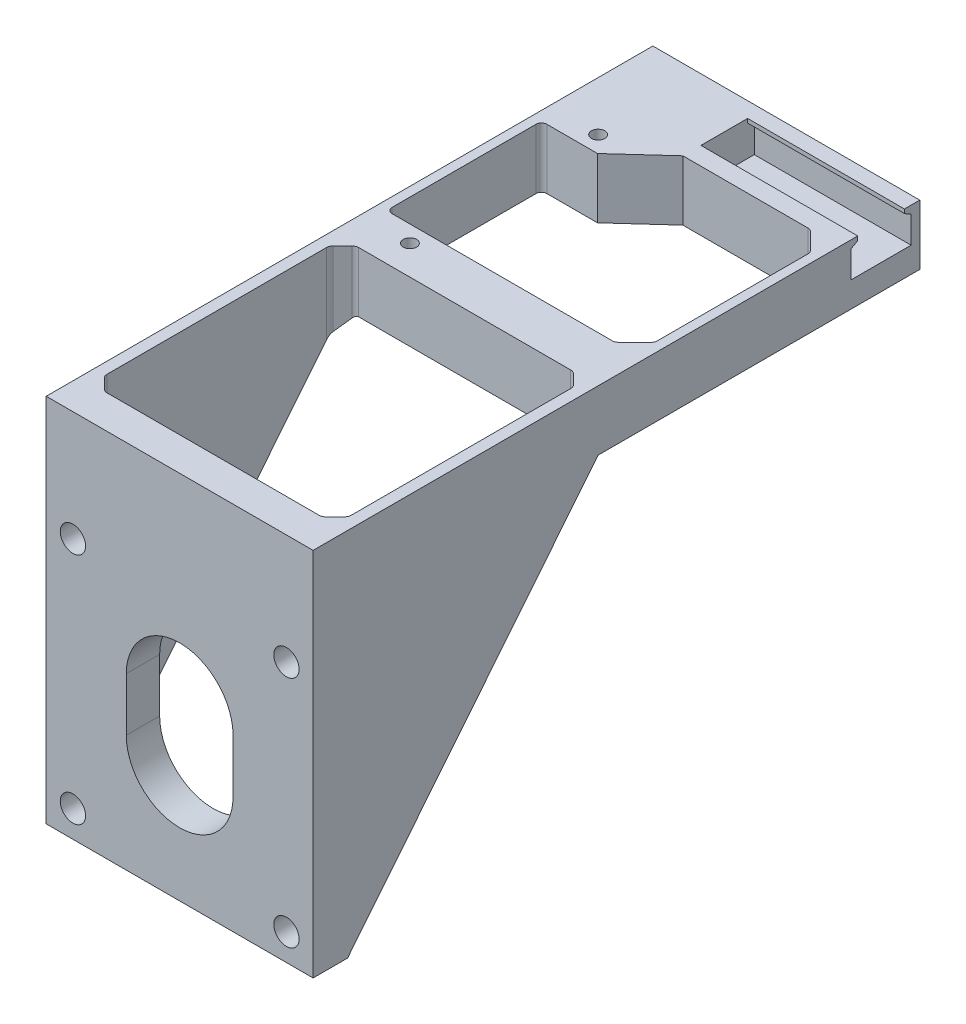
SolidWorks part; units mm, degrees
ref_plane "Front Plane" through (0, 0, 0) normal (0, 0, 1) x (1, 0, 0)
ref_plane "Top Plane" through (0, 0, 0) normal (0, 1, 0) x (1, 0, 0)
ref_plane "Right Plane" through (0, 0, 0) normal (1, 0, 0) x (0, 0, -1)
sketch "Sketch1" plane through (0, 0, 0) normal (0, 1, 0) x (1, 0, 0)
  line L0 (0, 0) -> (0, 59.6401) construction
  line L1 (-20, -19.2885) -> (-21.4, -19.2885)
  line L2 (20, 17.7115) -> (21.4, 17.7115)
  line L3 (20, 17.7115) -> (20, 69.9115)
  line L4 (20, 69.9115) -> (21.4, 69.9115)
  line L5 (21.4, 17.7115) -> (21.4, 69.9115)
  line L6 (20, 17.7115) -> (21.4, 17.7115)
  line L7 (20, 17.7115) -> (20, -19.2885)
  line L8 (20, -19.2885) -> (21.4, -19.2885)
  line L9 (21.4, 17.7115) -> (21.4, -19.2885)
  line L10 (-21.4, 17.7115) -> (-21.4, -19.2885)
  line L11 (-20, 17.7115) -> (-21.4, 17.7115)
  line L12 (-20, 17.7115) -> (-20, -19.2885)
  line L13 (-20, 69.9115) -> (-21.4, 69.9115)
  line L14 (-21.4, 17.7115) -> (-21.4, 69.9115)
  line L15 (-20, 17.7115) -> (-21.4, 17.7115)
  line L16 (-20, 17.7115) -> (-20, 69.9115)
  dimension "18" = 20
  dimension "D2" = 1.4
  dimension "D3" = 37
  dimension "D4" = 52.2
extrude "Boss-Extrude1" add sketch "Sketch1" against normal blind 9 from offset 1 contours L12 L11 L10 L1 | L11 L16 L13 L14 | L3 L2 L5 L4 offset against normal yes
sketch "Sketch4" plane through (0, -10, 0) normal (0, -1, 0) x (1, 0, 0)
  line L0 (-21.4, -69.9115) -> (-21.4, 19.2885) construction
  line L1 (18.6, -69.9115) -> (-21.4, -69.9115)
  line L2 (18.6, -69.9115) -> (18.6, -57.9115)
  line L3 (18.6, -57.9115) -> (-21.4, -57.9115)
  line L4 (-21.4, -69.9115) -> (-21.4, -57.9115)
  line L13 (-20, -69.9115) -> (-21.4, -69.9115) construction
  dimension "D1" = 12
  dimension "D2" = 40
extrude "Boss-Extrude3" add sketch "Sketch4" against normal up to surface (9 mm away)
sketch "Sketch3" plane through (0, -10, 0) normal (0, -1, 0) x (1, 0, 0)
  line L0 (-21.4, -69.9115) -> (-21.4, 19.2885) construction
  line L1 (-21.4, -58.8115) -> (-7.4, -58.8115)
  line L2 (-21.4, -58.8115) -> (-21.4, -51.8115)
  line L3 (-21.4, -51.8115) -> (-7.4, -51.8115)
  line L4 (-7.4, -58.8115) -> (-7.4, -51.8115)
  line L6 (0, 0) -> (0, -31.4212) construction
  line L13 (18.6, -69.9115) -> (-21.4, -69.9115) construction
  line L14 (-21.4, -40.2115) -> (-3.8096, -40.2115) construction
  line L15 (-21.4, -28.6115) -> (-7.4, -28.6115)
  line L16 (-7.4, -21.6115) -> (-7.4, -28.6115)
  line L17 (-21.4, -21.6115) -> (-7.4, -21.6115)
  line L18 (-21.4, -21.6115) -> (-21.4, -28.6115)
  line L19 (-20, -57.9115) -> (-20, 19.2885) construction
  circle A0 centre (-14, -54.3115) radius 1
  circle A2 centre (-14, -26.1115) radius 1
  dimension "D4" = 2.5
  dimension "D5" = 2
  dimension "D1" = 14.1
  dimension "D2" = 15.6
  dimension "D3" = 7
  dimension "D6" = 6
  dimension "D7" = 14
extrude "Servo Holder" add sketch "Sketch3" along normal blind 1 and the other way offset from surface (9 mm away) 1 other way up to plane "Top Plane"
sketch "Sketch37" plane through (0, -1, 0) normal (0, 1, 0) x (1, 0, 0)
  line L0 (-7.4, 21.6115) -> (-20, 21.6115) construction
  line L1 (18.6, 21.6115) -> (-7.4, 21.6115)
  line L2 (18.6, 21.6115) -> (18.6, 28.6115)
  line L3 (18.6, 28.6115) -> (-7.4, 28.6115)
  line L4 (-7.4, 21.6115) -> (-7.4, 28.6115)
  line L5 (-21.4, 69.9115) -> (-21.4, -19.2885) construction
  dimension "D1" = 40
extrude "Boss-Extrude19" add sketch "Sketch37" against normal up to surface (10 mm away) up to face at (-14.4, -11, -25.1115)
sketch "Sketch29" plane through (0, 0, -69.9115) normal (0, 0, -1) x (-1, 0, 0)
  line L1 (21.4, -10) -> (-27.4015, -10)
  line L2 (21.4, -10) -> (21.4, -16.1774)
  line L3 (21.4, -16.1774) -> (-27.4015, -16.1774)
  line L4 (-27.4015, -10) -> (-27.4015, -16.1774)
extrude "Cut-Extrude10" cut sketch "Sketch29" against normal through all both and the other way through all
sketch "Sketch35" plane through (18.6, 0, 0) normal (1, 0, 0) x (0, 0, -1)
  line L0 (-2, -1) -> (21.6115, -1)
  line L1 (21.6115, -1) -> (21.6115, -10)
  line L4 (-19.2885, -1) -> (-2, -1)
  line L5 (21.6115, -10) -> (21.6115, -1) construction
  line L6 (-19.2885, -10) -> (-19.2885, -1) construction
  line L9 (21.6115, -1) -> (28.6115, -1) construction
  line L11 (21.6115, -10) -> (-19.2885, -10)
  line L12 (-19.2885, -10) -> (-19.2885, -1)
  line L13 (69.9115, -10) -> (-19.2885, -10) construction
extrude "Boss-Extrude17" add sketch "Sketch35" against normal blind 3
sketch "Sketch39" plane through (0, -1, 0) normal (0, 1, 0) x (1, 0, 0)
  line L0 (-21.4, 69.9115) -> (18.6, 69.9115) construction
  line L1 (18.6, 28.6115) -> (17.2, 28.6115)
  line L2 (18.6, 28.6115) -> (18.6, 69.9115)
  line L3 (18.6, 69.9115) -> (17.2, 69.9115)
  line L4 (17.2, 28.6115) -> (17.2, 69.9115)
  line L5 (-20, 28.6115) -> (18.6, 28.6115) construction
  line L6 (18.6, -19.2885) -> (18.6, 28.6115) construction
  point P7 (18.6, 49.2615)
  dimension "D1" = 1.4
extrude "Boss-Extrude20" add sketch "Sketch39" against normal up to surface (9 mm away) up to face at (-2.2857, -10, -27.3258)
sketch "Sketch40" plane through (18.6, 0, 0) normal (1, 0, 0) x (0, 0, -1)
  line L0 (-19.2885, -1) -> (69.9115, -1) construction
  line L1 (60.6115, -1) -> (67.6115, -1)
  line L2 (69.9115, -1) -> (69.9115, -10) construction
  line L6 (60.6115, -2.2) -> (59.6115, -2.2)
  line L7 (59.6115, -2.2) -> (59.6115, -6.2)
  line L8 (59.6115, -6.2) -> (68.6115, -6.2)
  line L9 (64.1115, -6.2) -> (64.1115, -1)
  line L13 (67.6115, -1) -> (67.6115, -2.2)
  line L15 (60.6115, -2.2) -> (60.6115, -1)
  line L17 (68.6115, -2.2) -> (68.6115, -6.2)
  line L18 (67.6115, -2.2) -> (68.6115, -2.2)
  point P9 (59.6115, -4.2)
  dimension "D1" = 5.8
  dimension "D2" = 3.5
  dimension "D3" = 4.5
  dimension "D4" = 4
  dimension "D5" = 1.2
  dimension "D6" = 3.5
extrude "Cut-Extrude13" cut sketch "Sketch40" against normal offset from surface (23.5 mm away) 16.5
chamfer "Chamfer2" distance 0.6 angle 60 2 edges at (6.85, -2.2, -60.6115) (6.85, -2.2, -67.6115)
chamfer "Chamfer3" distance 3 angle 45 2 edges at (17.2, -5.5, -28.6115) (17.2, -5.5, -57.9115)
chamfer "Chamfer4" distance 2.5 angle 45 1 edges at (-7.4, -5.5, -57.9115)
sketch "Sketch43" plane through (0, -1, 0) normal (0, 1, 0) x (1, 0, 0)
  line L0 (-4.9, 57.9115) -> (-11.6, 51.8115)
  line L1 (-7.4, 51.8115) -> (-20, 51.8115) construction
  line L2 (-11.6, 51.8115) -> (-4.9, 51.8115)
  line L3 (-4.9, 51.8115) -> (-4.9, 57.9115)
extrude "Cut-Extrude16" cut sketch "Sketch43" against normal blind 10
fillet "Fillet11" radius 0.8 6 edges at (-20, -5.5, -51.8115) (-20, -5.5, -28.6115) (14.2, -5.5, -28.6115) (17.2, -5.5, -31.6115) (17.2, -5.5, -54.9115) (14.2, -5.5, -57.9115)
sketch "Sketch51" plane through (0, -1, 0) normal (0, 1, 0) x (1, 0, 0)
  line L0 (18.6, -19.2885) -> (18.6, 60.6115) construction
  line L1 (-21.4, -19.2885) -> (18.6, -19.2885)
  line L2 (-21.4, -19.2885) -> (-21.4, 21.7115)
  line L3 (-21.4, 21.7115) -> (18.6, 21.7115)
  line L4 (18.6, -19.2885) -> (18.6, 21.7115)
extrude "Cut-Extrude17" cut sketch "Sketch51" against normal blind 10
ref_plane "Plane1" through (0, 0, 16) normal (0, 0, 1) x (1, 0, 0)
sketch "Sketch50" plane through (0, 0, 16) normal (0, 0, 1) x (1, 0, 0)
  line L0 (-1.4, -5) -> (-1.4, -71.7325) construction
  line L1 (-21.4, -35) -> (18.6, -35) construction
  line L2 (-21.4, -1) -> (18.6, -1)
  line L3 (-21.4, -1) -> (-21.4, -56.5)
  line L4 (-21.4, -56.5) -> (18.6, -56.5)
  line L5 (18.6, -1) -> (18.6, -56.5)
  line L6 (-1.4, -31) -> (-1.4, -39) construction
  line L7 (6.6, -31) -> (6.6, -39)
  line L8 (-9.4, -31) -> (-9.4, -39)
  line L10 (18.6, -10) -> (18.6, -1) construction
  line L11 (18.6, -1) -> (-21.4, -1) construction
  circle A0 centre (-17.4, -17.5) radius 1.9
  circle A1 centre (14.6, -17.5) radius 1.9
  circle A2 centre (14.6, -52.5) radius 1.9
  circle A3 centre (-17.4, -52.5) radius 1.9
  arc A4 (6.6, -31) -> (-9.4, -31) centre (-1.4, -31) ccw
  arc A5 (-9.4, -39) -> (6.6, -39) centre (-1.4, -39) ccw
  point P20 (-1.4, -35)
  dimension "D3" = 3.8
  dimension "D6" = 34
  dimension "D1" = 16
  dimension "D2" = 17.5
  dimension "D4" = 4
  dimension "D5" = 8
  dimension "D7" = 4
  dimension "D8" = 20
extrude "Boss-Extrude24" add sketch "Sketch50" along normal blind 5 separate body
sketch "Sketch53" plane through (0, -1, 0) normal (0, 1, 0) x (1, 0, 0)
  line L0 (-1.4, -16) -> (-1.4, 21.7115) construction
  line L1 (18.6, -16) -> (-21.4, -16) construction
  line L3 (18.6, -16) -> (18.6, 21.7115)
  line L4 (18.6, 21.7115) -> (16.9, 21.7115)
  line L5 (16.9, 21.7115) -> (16.9, -16)
  line L6 (16.9, -16) -> (18.6, -16)
  line L7 (-19.7, 21.7115) -> (-19.7, -16)
  line L8 (-21.4, 21.7115) -> (-19.7, 21.7115)
  line L9 (-21.4, -16) -> (-21.4, 21.7115)
  line L10 (-19.7, -16) -> (-21.4, -16)
  point P4 (0, 0)
  dimension "D1" = 1.7
extrude "Boss-Extrude25" add sketch "Sketch53" against normal up to surface (9 mm away)
chamfer "Chamfer6" distance 46.7 angle 38.92 2 edges at (17.75, -10, 16) (-20.55, -10, 16)
chamfer "Chamfer5" distance 2 angle 45 4 edges at (16.9, -28.75, 16) (-19.7, -28.75, 16) (16.9, -5.5, -21.7115) (-19.7, -5.5, -21.7115)
fillet "Fillet13" radius 1 12 edges at (16.9, -27.6116, 14) (14.9, -8.3119, 16) (14.9, -55.4381, 16) (-17.7, -55.4381, 16) (-17.7, -8.3119, 16) (-19.7, -27.6116, 14) (-17.7, -35, 16) (14.9, -35, 16) (-19.7, -6.7369, -19.7115) (-17.7, -5.5, -21.7115) (16.9, -6.7369, -19.7115) (14.9, -5.5, -21.7115)
